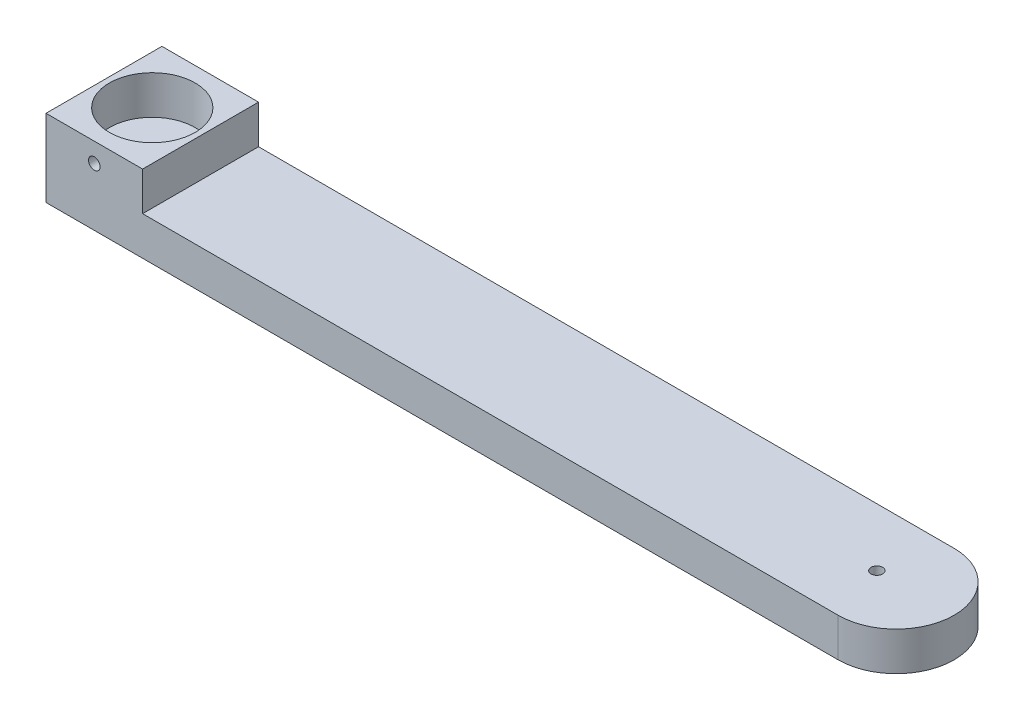
SolidWorks part; units mm, degrees
ref_plane "Front Plane" through (0, 0, 0) normal (0, 0, 1) x (1, 0, 0)
ref_plane "Top Plane" through (0, 0, 0) normal (0, 1, 0) x (1, 0, 0)
ref_plane "Right Plane" through (0, 0, 0) normal (1, 0, 0) x (0, 0, -1)
sketch "Sketch1" plane through (0, 0, 0) normal (0, 1, 0) x (1, 0, 0)
  line L1 (-110, -15) -> (110, -15)
  line L2 (-110, -15) -> (-110, 15)
  line L3 (-110, 15) -> (110, 15)
  line L4 (110, -15) -> (110, 15)
  line L5 (-110, -15) -> (110, 15) construction
  line L6 (-110, 15) -> (110, -15) construction
  circle A0 centre (95, 0) radius 15
  point P0 (0, 0)
  dimension "D3" = 30
  dimension "D1" = 220
  dimension "D2" = 30
extrude "Boss-Extrude1" add sketch "Sketch1" along normal blind 10 contours A0 L3 L2 L1 | A0 region at (-13.3615, 0, 0) region at (95, 0, 0)
sketch "Sketch2" plane through (0, 10, 0) normal (0, 1, 0) x (1, 0, 0)
  line L0 (-5.5, 0) -> (5.5, 0) construction
  line L2 (-85, -15) -> (-110, -15)
  line L3 (-85, -15) -> (-85, 15)
  line L4 (-85, 15) -> (-110, 15)
  line L5 (-110, -15) -> (-110, 15)
  line L6 (-85, -15) -> (-110, 15) construction
  line L7 (-85, 15) -> (-110, -15) construction
  circle A1 centre (-97.5, 0) radius 11.1
  dimension "D1" = 25
  dimension "D2" = 22.2
extrude "Boss-Extrude3" add sketch "Sketch2" along normal blind 10 contours L3 A1 region at (-97.5, 10, 14.6095)
sketch "Sketch4" plane through (0, 10, 0) normal (0, 1, 0) x (1, 0, 0)
  line L0 (-11, 0) -> (11, 0) construction
  circle A0 centre (90, 0) radius 4.1
  arc A1 (95, -15) -> (95, 15) centre (95, 0) ccw construction
  dimension "D1" = 8.2
  dimension "D2" = 5
sketch "Sketch6" plane through (0, 0, 15) normal (0, 0, 1) x (1, 0, 0)
  line L0 (-85, 10) -> (-110, 10) construction
  line L1 (-110, 20) -> (-110, 0) construction
  line L2 (-97.5, 20) -> (-97.5, 10) construction
  circle A0 centre (-97.5, 15) radius 1.5
  dimension "D1" = 3
extrude "Cut-Extrude2" cut sketch "Sketch6" against normal blind 10
extrude "Cut-Extrude3" cut sketch "Sketch4" along normal blind 6.5 from surface starting at face at (-3.75, 0, 0)
sketch "Sketch7" plane through (0, 6.5, 0) normal (0, -1, 0) x (-1, 0, 0)
  circle A0 centre (-90, 0) radius 1.5
  dimension "D1" = 3
extrude "Cut-Extrude4" cut sketch "Sketch7" against normal blind 14
sketch "Sketch8" plane through (0, 0, 0) normal (0, -1, 0) x (1, 0, 0)
  line L0 (87.5626, 4.1) -> (92.5569, 4.1) construction
  line L1 (92.5569, 4.1) -> (90, 0) construction
  line L2 (90, 0) -> (90, 4.1) construction
  line L3 (89.6, 4.1) -> (90.4, 4.1)
  line L4 (89.6, 4.1) -> (89.85, 3.4)
  line L5 (89.85, 3.4) -> (90.15, 3.4)
  line L6 (90.15, 3.4) -> (90.4, 4.1)
  line L7 (90, 4.1) -> (90, -4.1) construction
  circle A0 centre (90, 0) radius 4.1 construction
  circle A1 centre (90, 0) radius 4.1 construction
  point P8 (0, 0)
  point P16 (90, 0)
  dimension "D1" = 0.8
  dimension "D2" = 0.7
  dimension "D3" = 0.3
extrude "Boss-Extrude4" add sketch "Sketch8" against normal up to next
pattern_circular "CirPattern1" count 18 over 360 about axis through (90, 0, 0) along (0, 1, 0) of "Boss-Extrude4"
